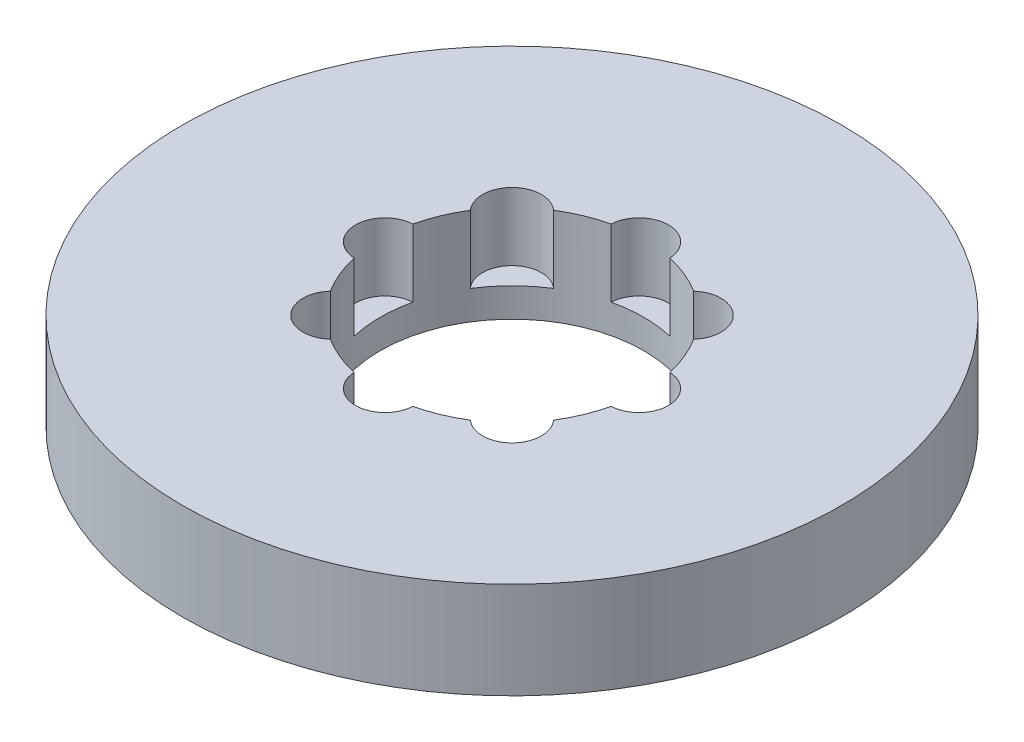
SolidWorks part; units mm, degrees
ref_plane "Front Plane" through (0, 0, 0) normal (0, 0, 1) x (1, 0, 0)
ref_plane "Top Plane" through (0, 0, 0) normal (0, 1, 0) x (1, 0, 0)
ref_plane "Right Plane" through (0, 0, 0) normal (1, 0, 0) x (0, 0, -1)
sketch "Sketch1" plane through (0, 0, 0) normal (0, 1, 0) x (1, 0, 0)
  circle A0 centre (0, 0) radius 37.5
  dimension "FLANGE_OD" = 75
extrude "Boss-Extrude1" add sketch "Sketch1" along normal blind 11
sketch "Sketch2" plane through (0, 0, 0) normal (0, 1, 0) x (1, 0, 0)
  circle A0 centre (0, 0) radius 15
  dimension "BORE_D" = 30
extrude "Cut-Extrude1" cut sketch "Sketch2" along normal through all
sketch "Sketch3" plane through (0, 11, 0) normal (0, 1, 0) x (1, 0, 0)
  circle A0 centre (0, 0) radius 14.4546 construction
  circle A1 centre (-14.4546, 0) radius 3.3497
  dimension "BOLT_D" = 6.6995
  dimension "BOLT_PCD" = 28.9092
extrude "Cut-Extrude2" cut sketch "Sketch3" against normal blind 7.7026
pattern_circular "CirPattern1" count 8 over 360 about axis through (0, 0, 0) along (0, 1, 0) of "Cut-Extrude2"
